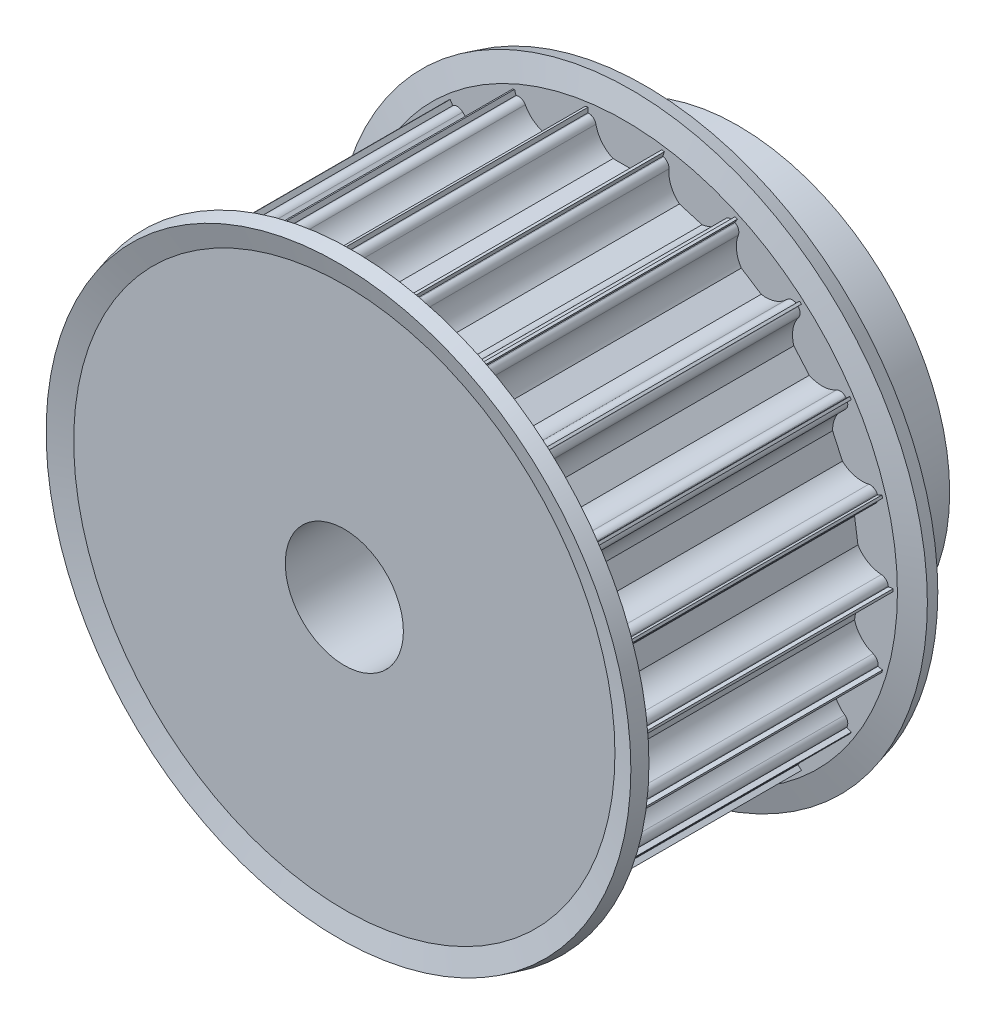
SolidWorks part; units mm, degrees
material "2219-T37"
ref_plane "Front Plane" through (0, 0, 0) normal (0, 0, 1) x (1, 0, 0)
ref_plane "Top Plane" through (0, 0, 0) normal (0, 1, 0) x (1, 0, 0)
ref_plane "Right Plane" through (0, 0, 0) normal (1, 0, 0) x (0, 0, -1)
sketch "Sketch1" plane through (0, 0, 0) normal (1, 0, 0) x (0, 0, -1)
  line L0 (0, 6) -> (0, 27.25)
  line L1 (0, 27.25) -> (30, 27.25)
  line L2 (30, 27.25) -> (30, 21.5)
  line L3 (30, 21.5) -> (40, 21.5)
  line L4 (40, 21.5) -> (40, 6)
  line L5 (40, 6) -> (0, 6)
  line L6 (-29.5361, 0) -> (53.0718, 0) construction
  dimension "D1" = 21.25
  dimension "D2" = 30
  dimension "D3" = 82.6079
  dimension "D4" = 10
  dimension "D5" = 15.5
  dimension "D6" = 40
  dimension "D7" = 6
revolve "Revolve1" add sketch "Sketch1" angle 360 about L6
sketch "Sketch2" plane through (0, 0, 0) normal (0, 0, 1) x (1, 0, 0)
  line L0 (3.6742, 26.5) -> (3.75, 26.5)
  line L1 (-3.75, 28.5) -> (3.75, 28.5)
  line L2 (-3.75, 28.5) -> (-3.75, 26.5)
  line L3 (-3.75, 26.5) -> (-3.6742, 26.5)
  line L4 (3.75, 28.5) -> (3.75, 26.5)
  line L5 (-1.199, 23.75) -> (1.199, 23.75)
  arc A0 (-2.9394, 25.9) -> (-1.199, 23.75) centre (0, 26.5) ccw
  arc A1 (-2.9394, 25.9) -> (-3.6742, 26.5) centre (-3.6742, 25.75) ccw
  arc A2 (2.9394, 25.9) -> (3.6742, 26.5) centre (3.6742, 25.75) cw
  arc A3 (1.199, 23.75) -> (2.9394, 25.9) centre (0, 26.5) ccw
  dimension "D1" = 3
  dimension "D5" = 0.75
  dimension "D6" = 0.75
  dimension "D2" = 2
  dimension "D3" = 7.5
  dimension "D4" = 26.5
  dimension "D7" = 2.75
extrude "Cut-Extrude1" cut sketch "Sketch2" against normal through all
sketch "Sketch3" plane through (0, 0, 0) normal (1, 0, 0) x (0, 0, -1)
  line L0 (-21.2099, 0) -> (61.6638, 0) construction
  dimension "D1" = 82.8737
pattern_circular "CirPattern1" count 22 over 360 about axis through (0, 0, 21.2099) along (0, 0, -1) of "Cut-Extrude1"
sketch "Sketch4" plane through (0, 0, 0) normal (1, 0, 0) x (0, 0, -1)
  line L0 (1.5, 27.6907) -> (0.0511, 27.3025) construction
  line L1 (0, 27.6907) -> (1.5, 27.6907) construction
  line L2 (0, 27.6907) -> (0, 22.6907)
  line L3 (0, 22.6907) -> (1.5, 22.6907)
  line L4 (1.5, 27.6907) -> (1.5, 22.6907)
  line L5 (1.5, 27.6907) -> (0.8569, 30.0907)
  line L6 (0.0511, 27.3025) -> (-0.592, 29.7025)
  line L7 (0.8569, 30.0907) -> (-0.592, 29.7025)
  line L8 (30, 26.9907) -> (0, 26.9907) construction
  line L9 (15, 37.195) -> (15, -35.9286) construction
  line L10 (0, 25.679) -> (0, 23.1257) construction
  line L11 (30, 27.6907) -> (28.5, 27.6907) construction
  line L12 (28.5, 27.6907) -> (29.9489, 27.3025) construction
  line L13 (29.1431, 30.0907) -> (30.592, 29.7025)
  line L14 (29.9489, 27.3025) -> (30.592, 29.7025)
  line L15 (28.5, 27.6907) -> (29.1431, 30.0907)
  line L16 (28.5, 27.6907) -> (28.5, 22.6907)
  line L17 (30, 22.6907) -> (28.5, 22.6907)
  line L18 (30, 27.6907) -> (30, 22.6907)
  dimension "D1" = 165
  dimension "D2" = 5
  dimension "D3" = 1.5
  dimension "D4" = 2.4
  dimension "D5" = 1.5
  dimension "D6" = 0.7
  dimension "D7" = 73.1236
  dimension "D8" = 0
revolve "Revolve2" add sketch "Sketch4" angle 360 about L0 region at (0, 26.3219, -0.6556) region at (0, 26.3219, -29.3444)
